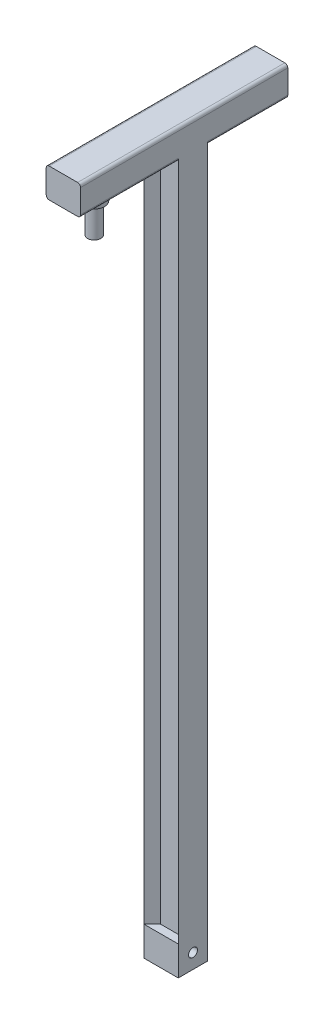
SolidWorks part; units mm, degrees
ref_plane "Front Plane" through (0, 0, 0) normal (0, 0, 1) x (1, 0, 0)
ref_plane "Top Plane" through (0, 0, 0) normal (0, 1, 0) x (1, 0, 0)
ref_plane "Right Plane" through (0, 0, 0) normal (1, 0, 0) x (0, 0, -1)
sketch "Sketch1" plane through (0, 0, 0) normal (0, 1, 0) x (1, 0, 0)
  line L0 (0, 0) -> (-2.8284, -2.8284)
  line L1 (-2.8284, -2.8284) -> (-8.8284, -2.8284)
  line L2 (-8.8284, -2.8284) -> (-11.6569, 0)
  line L3 (-11.6569, 0) -> (-11.6569, -10)
  line L4 (-11.6569, -10) -> (-8.8284, -7.1716)
  line L5 (-8.8284, -7.1716) -> (-2.8284, -7.1716)
  line L6 (-2.8284, -7.1716) -> (0, -10)
  line L7 (0, -10) -> (0, 0)
  dimension "D1" = 6
  dimension "D2" = 6
  dimension "D3" = 135
  dimension "D4" = 135
  dimension "D5" = 10
  dimension "D6" = 10
  dimension "D7" = 4
  dimension "D8" = 4
extrude "Boss-Extrude1" add sketch "Sketch1" along normal blind 240
sketch "Sketch2" plane through (0, 0, 0) normal (0, -1, 0) x (1, 0, 0)
  line L1 (0, 0) -> (-11.6569, 0)
  line L2 (0, 0) -> (0, 10)
  line L3 (0, 10) -> (-11.6569, 10)
  line L4 (-11.6569, 0) -> (-11.6569, 10)
extrude "Boss-Extrude2" add sketch "Sketch2" along normal blind 10
sketch "Sketch3" plane through (-11.6569, 0, 0) normal (-1, 0, 0) x (0, 0, 1)
  line L0 (10, -10) -> (0, -10) construction
  line L2 (0, -10) -> (0, 0) construction
  circle A0 centre (5, -5) radius 1.5
  point P4 (5, -10)
  point P7 (0, -5)
  dimension "D1" = 0
  dimension "D2" = 0
  dimension "D3" = 3
extrude "Cut-Extrude1" cut sketch "Sketch3" against normal blind 30
sketch "Sketch4" plane through (0, 0, 2.8284) normal (0, 0, -1) x (-1, 0, 0)
  line L0 (0, 240) -> (0, 0) construction
  line L1 (0, 240) -> (11.6569, 240)
  line L2 (0, 240) -> (0, 230)
  line L3 (0, 230) -> (11.6569, 230)
  line L4 (11.6569, 240) -> (11.6569, 230)
  line L5 (11.6569, 240) -> (11.6569, 0) construction
  line L6 (2.8284, 240) -> (8.8284, 240) construction
  dimension "D1" = 0
  dimension "D2" = 0
  dimension "D3" = 0
  dimension "D4" = 10
extrude "Boss-Extrude3" add sketch "Sketch4" along normal blind 30
sketch "Sketch5" plane through (0, 0, 7.1716) normal (0, 0, 1) x (1, 0, 0)
  line L0 (0, 240) -> (0, 0) construction
  line L1 (0, 240) -> (-11.6569, 240)
  line L2 (0, 240) -> (0, 230)
  line L3 (0, 230) -> (-11.6569, 230)
  line L4 (-11.6569, 240) -> (-11.6569, 230)
  line L5 (-8.8284, 240) -> (-2.8284, 240) construction
  dimension "D1" = 0
  dimension "D2" = 0
  dimension "D3" = 0
  dimension "D4" = 10
extrude "Boss-Extrude4" add sketch "Sketch5" along normal blind 36
sketch "Sketch7" plane through (0, 230, 0) normal (0, -1, 0) x (1, 0, 0)
  line L0 (-11.6569, 43.1716) -> (0, 43.1716) construction
  circle A0 centre (-5.8284, 32.7116) radius 2.25
  point P4 (-5.8284, 43.1716)
  dimension "D1" = 10.46
  dimension "D2" = 4.5
  dimension "D3" = 0
extrude "Boss-Extrude6" add sketch "Sketch7" along normal blind 13
sketch "Sketch8" plane through (0, 0, -27.1716) normal (0, 0, -1) x (-1, 0, 0)
  line L0 (0, 230) -> (11.6569, 230) construction
  line L1 (11.6569, 230) -> (11.6569, 240) construction
  circle A0 centre (5.8284, 235) radius 2.75
  point P4 (5.8284, 230)
  point P7 (11.6569, 235)
  dimension "D1" = 0
  dimension "D2" = 0
  dimension "D3" = 5.5
extrude "Cut-Extrude2" cut sketch "Sketch8" against normal blind 10
sketch "Sketch9" plane through (0, 230, 0) normal (0, -1, 0) x (-1, 0, 0)
  circle A1 centre (5.8284, -32.7116) radius 3.5
  dimension "D1" = 7
extrude "Boss-Extrude7" add sketch "Sketch9" along normal blind 3
thread "Thread1" pitch 2.1167 method cut profile "Thread Profile1" start angle 0, offset 0, length 8, pitch 2.1167, diameter 5.5
ref_plane "Plane1" through (-3.0784, 235, -27.1716) normal (0, -1, 0) x (1, 0, 0)
sketch "Thread Profile1" plane through (-3.0784, 235, -27.1716) normal (0, -1, 0) x (1, 0, 0)
  line L0 (0, 0) -> (0, 2.1167) construction
  line L1 (0, 0) -> (1.1457, 0.6615)
  line L2 (1.1457, 0.6615) -> (1.1457, 0.926)
  line L3 (1.1457, 0.926) -> (0, 1.5875)
  line L4 (1.1457, 0.7937) -> (0, 0.7937) construction
  line L11 (0, 0) -> (0, 1.5875)
  point P2 (0, 0)
  dimension "Pitch" = 2.1167
  dimension "Profile_Angle" = 60
  dimension "Profile_Land" = 0.2646
  dimension "Profile_Height" = 1.1457
sketch "Sketch12" plane through (0, 0, -27.1716) normal (0, 0, -1) x (-1, 0, 0)
  circle A0 centre (5.8284, 235) radius 3.75
  dimension "D1" = 7.5
extrude "Cut-Extrude3" cut sketch "Sketch12" against normal blind 2
fillet "Fillet1" radius 1 6 edges at (0, 240, 8) (0, 230, -13.5858) (-11.6569, 230, -13.5858) (-11.6569, 240, 8) (0, 230, 26.5858) (-11.6569, 230, 26.5858)
